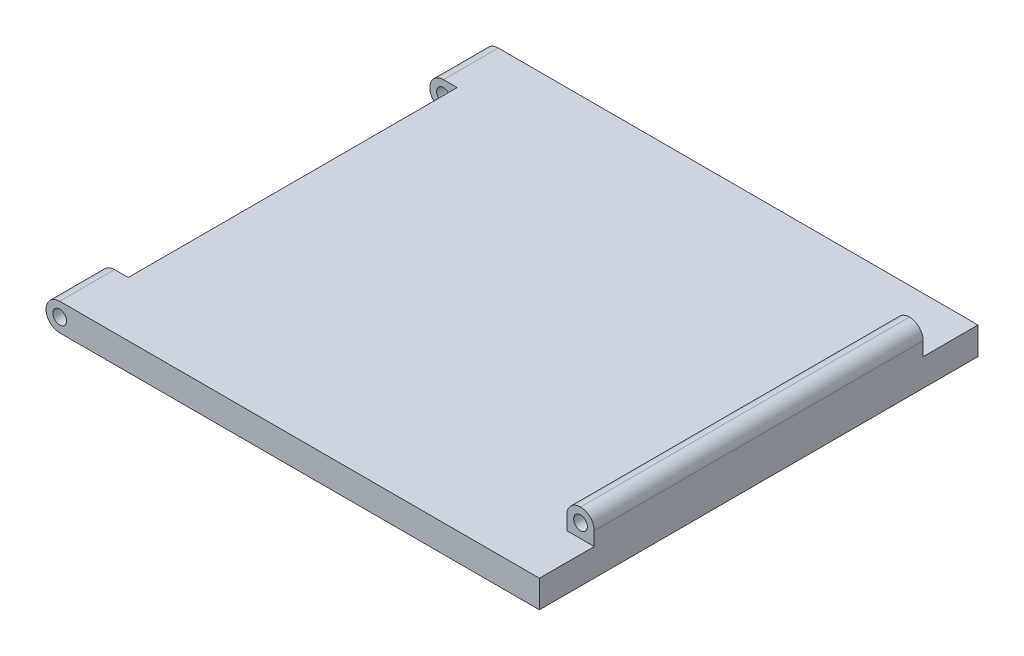
SolidWorks part; units mm, degrees
ref_plane "Front Plane" through (0, 0, 0) normal (0, 0, 1) x (1, 0, 0)
ref_plane "Top Plane" through (0, 0, 0) normal (0, 1, 0) x (1, 0, 0)
ref_plane "Right Plane" through (0, 0, 0) normal (1, 0, 0) x (0, 0, -1)
sketch "Sketch1" plane through (0, 0, 0) normal (0, 0, 1) x (1, 0, 0)
  line L0 (0, 0) -> (85, 0)
  line L1 (85, 0) -> (85, 10)
  line L2 (85, 10) -> (80, 10)
  line L3 (80, 10) -> (80, 5)
  line L4 (80, 5) -> (0, 5)
  line L5 (0, 5) -> (0, 0)
  dimension "D1" = 85
  dimension "D2" = 5
  dimension "D3" = 5
  dimension "D4" = 10
extrude "Boss-Extrude1" add sketch "Sketch1" along normal mid plane 80
sketch "Sketch2" plane through (0, 0, 0) normal (0, 0, 1) x (1, 0, 0)
  line L0 (0, 5) -> (-2.5, 5)
  line L1 (-2.5, 0) -> (0, 0)
  line L2 (0, 0) -> (0, 5)
  arc A0 (-2.5, 5) -> (-2.5, 0) centre (-2.5, 2.5) ccw
  circle A1 centre (-2.5, 2.5) radius 1.25
  dimension "D1" = 2.5
  dimension "D2" = 2.5
extrude "Boss-Extrude2" add sketch "Sketch2" along normal blind 10 from offset 30
mirror "Mirror2" about plane through (0, 0, 0) normal (0, 0, 1) of "Boss-Extrude2"
sketch "Sketch3" plane through (0, 0, 0) normal (0, 0, 1) x (1, 0, 0)
  line L0 (85, 0) -> (85, 10) construction
  line L1 (80, 10) -> (85, 10)
  line L2 (80, 10) -> (80, 5)
  line L3 (80, 5) -> (85, 5)
  line L4 (85, 10) -> (85, 5)
  dimension "D1" = 5
extrude "Cut-Extrude1" cut sketch "Sketch3" against normal blind 10 from offset 30 offset against normal yes
mirror "Mirror3" about plane through (0, 0, 0) normal (0, 0, 1) of "Cut-Extrude1"
sketch "Sketch4" plane through (0, 0, 0) normal (0, 0, 1) x (1, 0, 0)
  line L0 (85, 10) -> (80, 10) construction
  circle A0 centre (82.5, 7.5) radius 1.25
  point P5 (82.5, 10)
  dimension "D1" = 2.5
  dimension "D2" = 2.5
extrude "Cut-Extrude2" cut sketch "Sketch4" against normal through all both and the other way through all
fillet "Fillet1" radius 2.5 2 edges at (80, 10, 0) (85, 10, 0)
